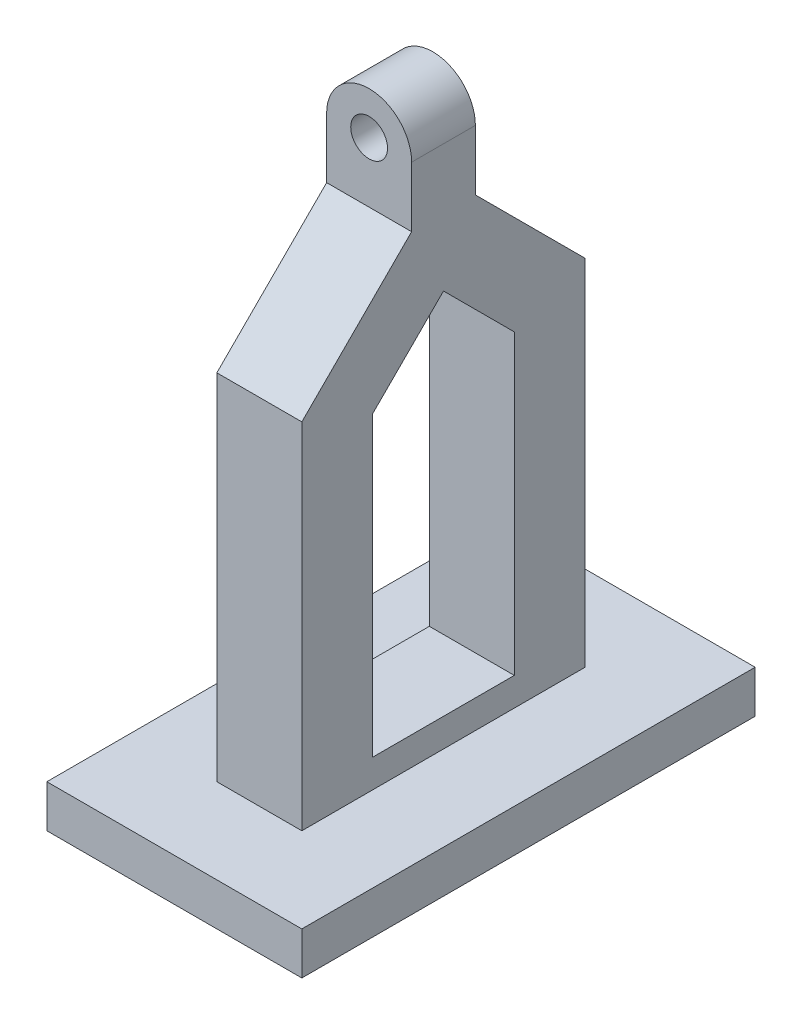
SolidWorks part; units mm, degrees
material "ABS"
ref_plane "Front Plane" through (0, 0, 0) normal (0, 0, 1) x (1, 0, 0)
ref_plane "Top Plane" through (0, 0, 0) normal (0, 1, 0) x (1, 0, 0)
ref_plane "Right Plane" through (0, 0, 0) normal (1, 0, 0) x (0, 0, -1)
sketch "Sketch2" plane through (0, 0, 0) normal (1, 0, 0) x (0, 0, -1)
  line L0 (12.7, 48.26) -> (-12.7, 48.26)
  line L2 (-12.7, 48.26) -> (-12.7, 0)
  line L3 (-12.7, 0) -> (12.7, 0)
  line L4 (12.7, 48.26) -> (12.7, 0)
  point P4 (0, 0)
  point P6 (0, 0)
  dimension "D1" = 25.4
  dimension "D2" = 48.26
extrude "Boss-Extrude1" add sketch "Sketch2" along normal mid plane 7.62
sketch "Sketch5" plane through (3.81, 0, 0) normal (1, 0, 0) x (0, 0, -1)
  line L1 (12.7, 48.26) -> (-12.7, 48.26) construction
  line L4 (6.35, 41.91) -> (-6.35, 41.91)
  line L5 (6.35, 39.37) -> (-6.35, 39.37)
  line L8 (-6.35, 6.35) -> (6.35, 6.35)
  line L9 (6.35, 6.35) -> (6.35, 41.91)
  line L11 (-6.35, 41.91) -> (-6.35, 6.35)
  line L13 (6.35, 6.35) -> (6.35, 39.37)
  line L15 (-6.35, 39.37) -> (-6.35, 6.35)
  line L16 (-6.35, 6.35) -> (6.35, 6.35)
  dimension "D2" = 8.89
  dimension "D1" = 6.35
extrude "Cut-Extrude2" cut sketch "Sketch5" against normal through all
sketch "Sketch4" plane through (0, 0, 0) normal (0, 1, 0) x (1, 0, 0)
  line L8 (-11.43, 20.32) -> (-11.43, -20.32)
  line L9 (11.43, 20.32) -> (-11.43, 20.32)
  line L10 (11.43, -20.32) -> (11.43, 20.32)
  line L11 (-11.43, -20.32) -> (11.43, -20.32)
  line L12 (-11.43, 20.32) -> (-11.43, -20.32)
  line L13 (11.43, 20.32) -> (-11.43, 20.32)
  line L14 (11.43, -20.32) -> (11.43, 20.32)
  line L15 (-11.43, -20.32) -> (11.43, -20.32)
  dimension "D1" = 7.62
extrude "Boss-Extrude3" add sketch "Sketch4" along normal blind 3.81
chamfer "Chamfer1" distance 6.35 angle 45 2 edges at (0, 39.37, 6.35) (0, 39.37, -6.35)
sketch "Sketch9" plane through (0, 0, 0) normal (0, 0, 1) x (1, 0, 0)
  line L0 (3.81, 48.26) -> (3.81, 3.81) construction
  line L1 (-3.81, 48.26) -> (3.81, 48.26)
  line L2 (-3.81, 48.26) -> (-3.81, 54.61)
  line L3 (-3.81, 54.61) -> (3.81, 54.61)
  line L4 (3.81, 48.26) -> (3.81, 54.61)
  dimension "D1" = 6.35
extrude "Boss-Extrude4" add sketch "Sketch9" along normal mid plane 5.715
hole_wizard "M3 Clearance Hole1" positions "Sketch6" profile "Sketch7" hole size "M3" standard "ANSI Metric" end condition through all
sketch "Sketch6" plane through (0, 0, -12.7) normal (0, 0, -1) x (-1, 0, 0)
  line L6 (3.175, 50.8) -> (3.175, 57.15)
  line L7 (3.175, 57.15) -> (-3.175, 57.15)
  line L8 (-3.175, 57.15) -> (-3.175, 50.8)
  line L9 (3.175, 50.8) -> (3.175, 57.15) construction
  line L10 (3.175, 57.15) -> (-3.175, 57.15) construction
  line L11 (-3.175, 57.15) -> (-3.175, 50.8) construction
  arc A2 (-3.175, 50.8) -> (3.175, 50.8) centre (0, 50.8) ccw
  arc A3 (-3.175, 50.8) -> (3.175, 50.8) centre (0, 50.8) ccw construction
  point P0 (0, 50.8)
  point P22 (0, 0)
  point P23 (0, 0)
  point P24 (0, 0)
  point P25 (0, 50.8)
  dimension "D1" = 0
sketch "Sketch7" plane through (0, 50.8, -12.7) normal (1, 0, 0) x (0, 1, 0)
  line L0 (0, 0) -> (0, 33.02)
  line L1 (0, 33.02) -> (1.65, 33.02)
  line L2 (1.65, 33.02) -> (1.65, 0)
  line L5 (1.65, 0) -> (0, 0)
  line L11 (0, -6.35) -> (0, 107.95) construction
  dimension "Thru Hole Dia." = 3.3
  dimension "Thru Hole Depth" = 33.02
chamfer "Chamfer2" distance 12.7 angle 45 2 edges at (0, 48.26, -12.7) (0, 48.26, 12.7)
sketch "Sketch8" plane through (0, 0, 12.7) normal (0, 0, 1) x (1, 0, 0)
  line L0 (3.81, 35.56) -> (3.81, 3.81) construction
  line L1 (-3.81, 35.56) -> (-3.81, 3.81) construction
  arc A0 (3.81, 50.8) -> (-3.81, 50.8) centre (0, 50.8) ccw
  circle A1 centre (0, 50.8) radius 1.65 construction
  point P3 (0, 0)
extrude "Cut-Extrude3" cut sketch "Sketch8" against normal through all and the other way through all flip side to cut
equation "\"2.156i\"=2.156"
